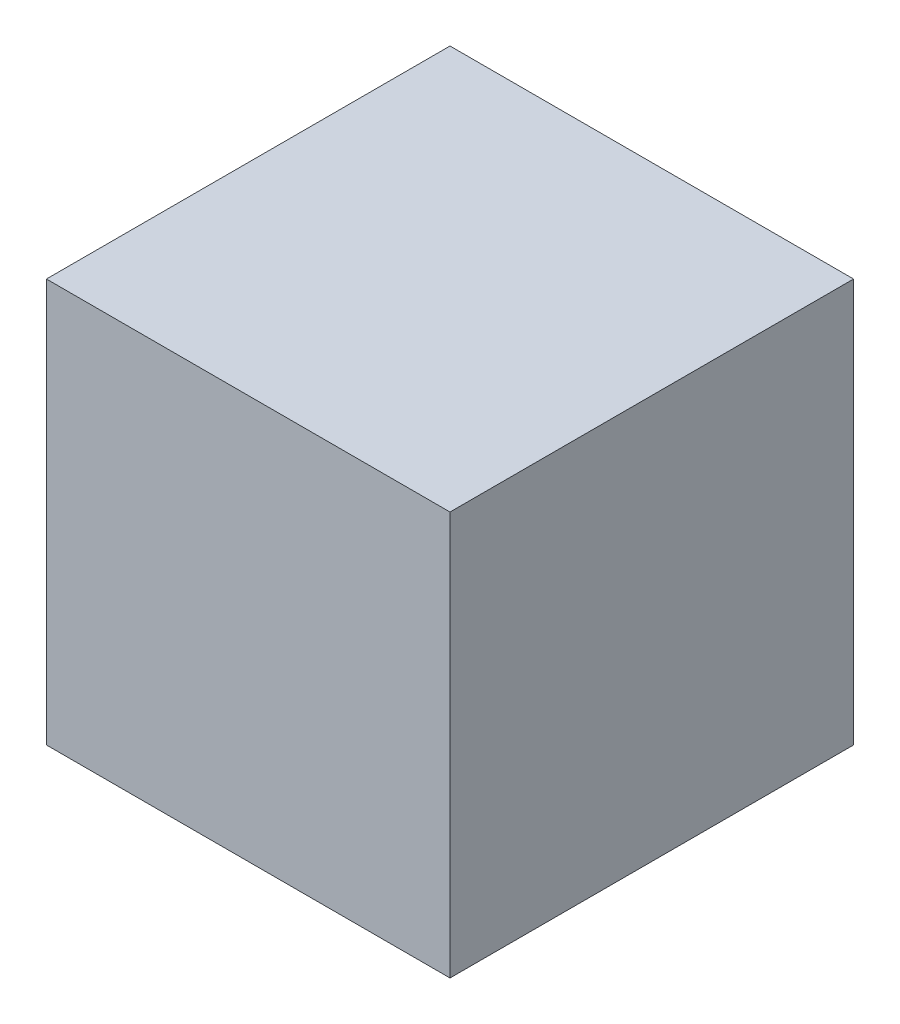
SolidWorks part; units mm, degrees
ref_plane "Front Plane" through (0, 0, 0) normal (0, 0, 1) x (1, 0, 0)
ref_plane "Top Plane" through (0, 0, 0) normal (0, 1, 0) x (1, 0, 0)
ref_plane "Right Plane" through (0, 0, 0) normal (1, 0, 0) x (0, 0, -1)
sketch "Sketch1" plane through (0, 0, 0) normal (0, 1, 0) x (1, 0, 0)
  line L1 (-30, -30) -> (30, -30)
  line L2 (-30, -30) -> (-30, 30)
  line L3 (-30, 30) -> (30, 30)
  line L4 (30, -30) -> (30, 30)
  line L5 (-30, -30) -> (30, 30) construction
  line L6 (-30, 30) -> (30, -30) construction
  point P0 (0, 0)
  dimension "D1" = 60
extrude "Boss-Extrude1" add sketch "Sketch1" along normal blind 30 and the other way blind 30
